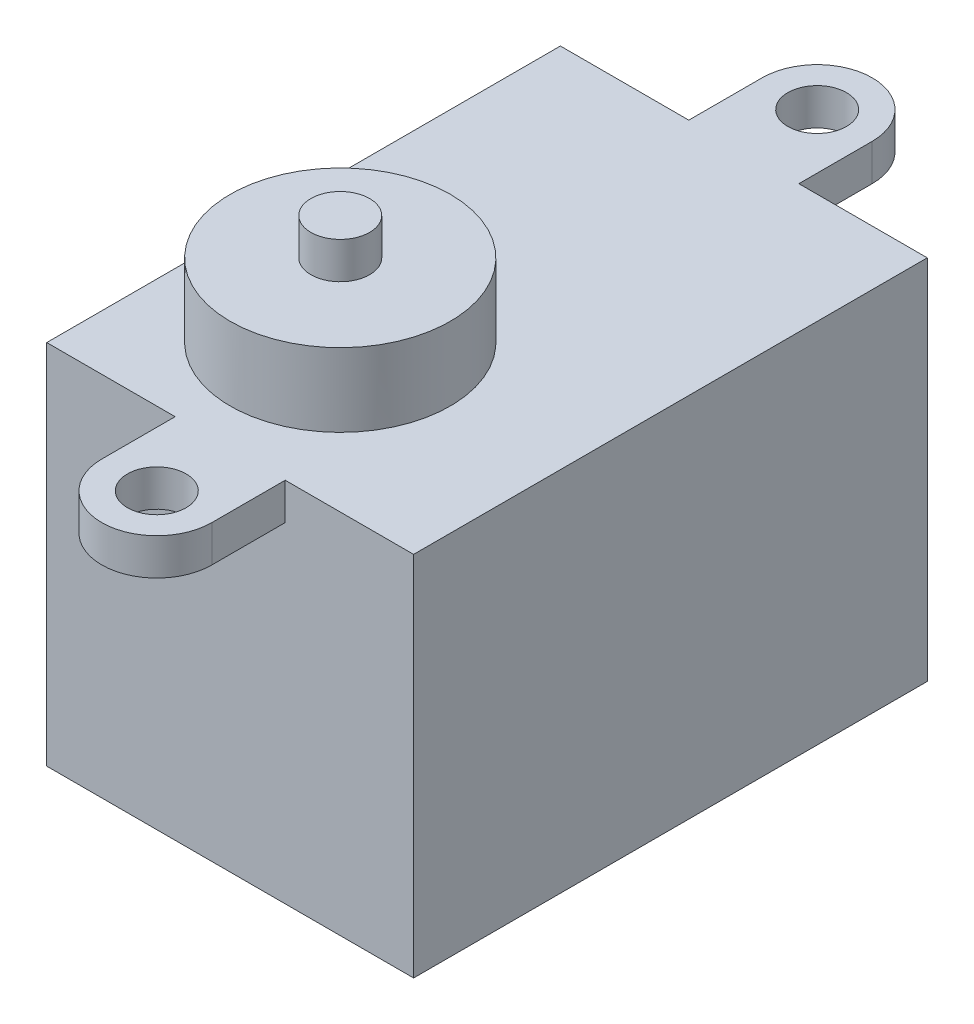
SolidWorks part; units mm, degrees
ref_plane "Front Plane" through (0, 0, 0) normal (0, 0, 1) x (1, 0, 0)
ref_plane "Top Plane" through (0, 0, 0) normal (0, 1, 0) x (1, 0, 0)
ref_plane "Right Plane" through (0, 0, 0) normal (1, 0, 0) x (0, 0, -1)
sketch "Sketch1" plane through (0, 0, 0) normal (0, 1, 0) x (1, 0, 0)
  line L1 (0, 0) -> (50, 0)
  line L2 (0, 0) -> (0, 70)
  line L3 (0, 70) -> (50, 70)
  line L4 (50, 0) -> (50, 70)
  dimension "D1" = 50
  dimension "D2" = 70
extrude "Boss-Extrude1" add sketch "Sketch1" along normal blind 50
sketch "Sketch2" plane through (0, 50, 0) normal (0, 1, 0) x (1, 0, 0)
  line L0 (0, 0) -> (50, 0) construction
  line L1 (0, 70) -> (0, 0) construction
  circle A0 centre (20, 20) radius 15
  dimension "D1" = 30
  dimension "D2" = 20
  dimension "D3" = 20
extrude "Boss-Extrude2" add sketch "Sketch2" along normal blind 10
sketch "Sketch3" plane through (0, 60, 0) normal (0, 1, 0) x (1, 0, 0)
  circle A0 centre (20, 20) radius 4
  dimension "D1" = 8
extrude "Boss-Extrude3" add sketch "Sketch3" along normal blind 5
shell "Shell7" thickness 2
sketch "Sketch4" plane through (0, 50, 0) normal (0, 1, 0) x (1, 0, 0)
  line L0 (50, 70) -> (0, 70) construction
  line L1 (17.5, 70) -> (32.5, 70)
  line L2 (17.5, 70) -> (17.5, 80)
  line L4 (32.5, 70) -> (32.5, 80)
  line L5 (25, 0) -> (25, 70) construction
  line L6 (0, 0) -> (50, 0) construction
  arc A0 (32.5, 80) -> (17.5, 80) centre (25, 80) ccw
  circle A1 centre (25, 80) radius 4
  dimension "D3" = 8
  dimension "D1" = 15
  dimension "D2" = 10
extrude "Boss-Extrude4" add sketch "Sketch4" against normal blind 5
ref_plane "Plane1" through (0, 0, -35) normal (0, 0, -1) x (-1, 0, 0)
mirror "Mirror1" about plane through (0, 0, -35) normal (0, 0, -1) of "Boss-Extrude4"
ref_axis "Axis1" through (20, 60, -20) along (0, -1, 0)
